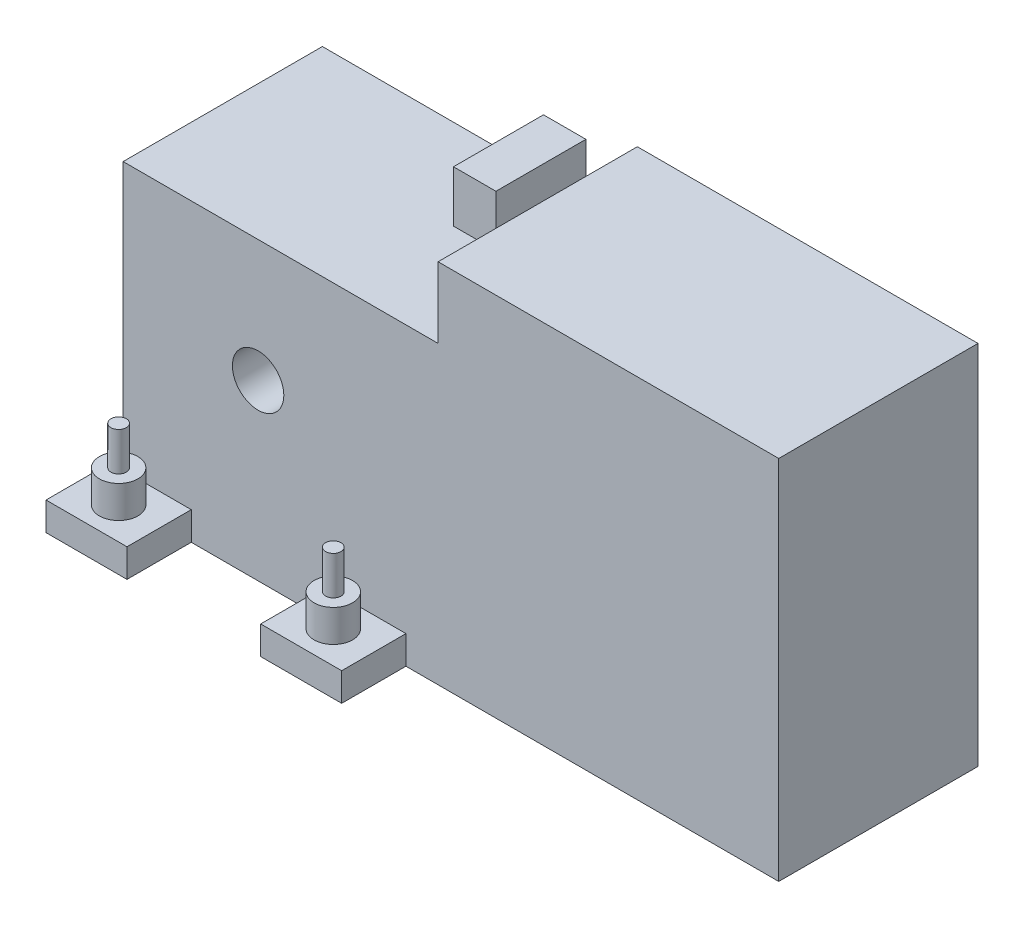
SolidWorks part; units mm, degrees
ref_plane "Front Plane" through (0, 0, 0) normal (0, 0, 1) x (1, 0, 0)
ref_plane "Top Plane" through (0, 0, 0) normal (0, 1, 0) x (1, 0, 0)
ref_plane "Right Plane" through (0, 0, 0) normal (1, 0, 0) x (0, 0, -1)
sketch "Sketch2" plane through (0, 0, 0) normal (0, 0, 1) x (1, 0, 0)
  circle A0 centre (0, 0) radius 85
  circle A1 centre (0, 0) radius 20
  dimension "D1" = 170
  dimension "D2" = 40
extrude "Boss-Extrude1" add sketch "Sketch2" along normal blind 5 contours A0 A1 region at (-82.5958, 0, 0)
sketch "Sketch3" plane through (0, 0, 0) normal (0, 0, -1) x (-1, 0, 0)
  line L1 (-405, 150) -> (-140, 150)
  line L2 (-405, 150) -> (-405, -135)
  line L3 (-405, -135) -> (-140, -135)
  line L4 (-140, 150) -> (-140, -135)
  line L5 (105, 95) -> (-140, 95)
  line L6 (105, 95) -> (105, -135)
  line L7 (105, -135) -> (-140, -135)
  line L8 (-140, 95) -> (-140, -135)
  circle A4 centre (0, 0) radius 85 construction
  circle A5 centre (0, 0) radius 85 construction
  circle M5 centre (0, 0) radius 20
  circle M6 centre (0, 0) radius 85
  dimension "D5" = 55
  dimension "D7" = 10
  dimension "D1" = 230
  dimension "D2" = 55
  dimension "D3" = 265
  dimension "D4" = 20
  dimension "D6" = 510
extrude "Boss-Extrude2" add sketch "Sketch3" along normal blind 155 contours L7 L6 L5 L4 M6 | L4 L1 L2 L3 | M6 M5 region at (272.5, 7.5, 0) region at (17.5, 91.6396, 0) region at (82.5958, 0, 0)
ref_point "Point2"
ref_point "Point4"
ref_axis "x" through (0, 0, 5) along (0, 0, -1)
ref_axis "y" through (0, 0, 5) along (-1, 0, 0)
ref_axis "z" through (0, 0, 5) along (0, 1, 0)
sketch "Sketch4" plane through (0, 0, -155) normal (0, 0, -1) x (-1, 0, 0)
  line L0 (105, 95) -> (-140, 95) construction
  line L1 (-100, 95) -> (-67, 95)
  line L2 (-100, 95) -> (-100, 135)
  line L3 (-100, 135) -> (-67, 135)
  line L4 (-67, 95) -> (-67, 135)
  line L5 (-140, 150) -> (-140, 95) construction
  line L6 (-405, 150) -> (-405, -135) construction
  line L7 (-67, 95) -> (-405, 95)
  line L8 (-67, 95) -> (-67, 135)
  line L9 (-67, 135) -> (-405, 135)
  line L10 (-405, 95) -> (-405, 135)
  line M11 (105, 95) -> (-140, 95)
  dimension "D1" = 33
  dimension "D2" = 40
  dimension "D3" = 40
extrude "Boss-Extrude4" add sketch "Sketch4" against normal blind 70 contours L4 L3 L2 M11 region at (83.5, 115, -155)
sketch "Sketch6" plane through (0, -135, 0) normal (0, -1, 0) x (1, 0, 0)
  line L0 (-105, 0) -> (405, 0) construction
  line L1 (-115, 0) -> (-52, 0)
  line L2 (-115, 0) -> (-115, 50)
  line L3 (-115, 50) -> (-52, 50)
  line L4 (-52, 0) -> (-52, 50)
  line L5 (-52, 50) -> (-115, 0) construction
  line L6 (0, 0) -> (0, 99.6978) construction
  line L7 (115, 50) -> (52, 50)
  line L8 (52, 0) -> (52, 50)
  line L9 (115, 0) -> (52, 0)
  line L10 (115, 0) -> (115, 50)
  circle A0 centre (-83.5, 25) radius 6
  circle A1 centre (-83.5, 25) radius 15
  circle A2 centre (83.5, 25) radius 6
  circle A3 centre (83.5, 25) radius 15
  line M8 (405, 0) -> (-105, 0)
  dimension "D2" = 12
  dimension "D3" = 30
  dimension "D5" = 197
  dimension "D1" = 63
  dimension "D4" = 50
extrude "Boss-Extrude6" add sketch "Sketch6" against normal blind 22 contours L4 L3 L2 L1 A1 M8 | L10 L7 L8 A3 M8 region at (-114.1957, -135, 25) region at (52.8043, -135, 25)
extrude "Boss-Extrude7" add sketch "Sketch6<3>" against normal blind 47 contours A1 A0 | A3 A2 region at (-98.0757, -135, 25) region at (68.9243, -135, 25)
sketch "Sketch6<3>" plane through (0, -135, 0) normal (0, -1, 0) x (1, 0, 0) same geometry as "Sketch6"
extrude "Boss-Extrude8" add sketch "Sketch6<4>" against normal blind 77 contours A0 | A2 region at (-83.5, -135, 25) region at (83.5, -135, 25)
sketch "Sketch6<4>" plane through (0, -135, 0) normal (0, -1, 0) x (1, 0, 0) same geometry as "Sketch6"
extrude "Cut-Extrude2" cut sketch "Sketch2<4>" against normal blind 5 from surface contours A0 starting at face at (20, 0, 5)
sketch "Sketch2<4>" plane through (0, 0, 0) normal (0, 0, 1) x (1, 0, 0) same geometry as "Sketch2"
